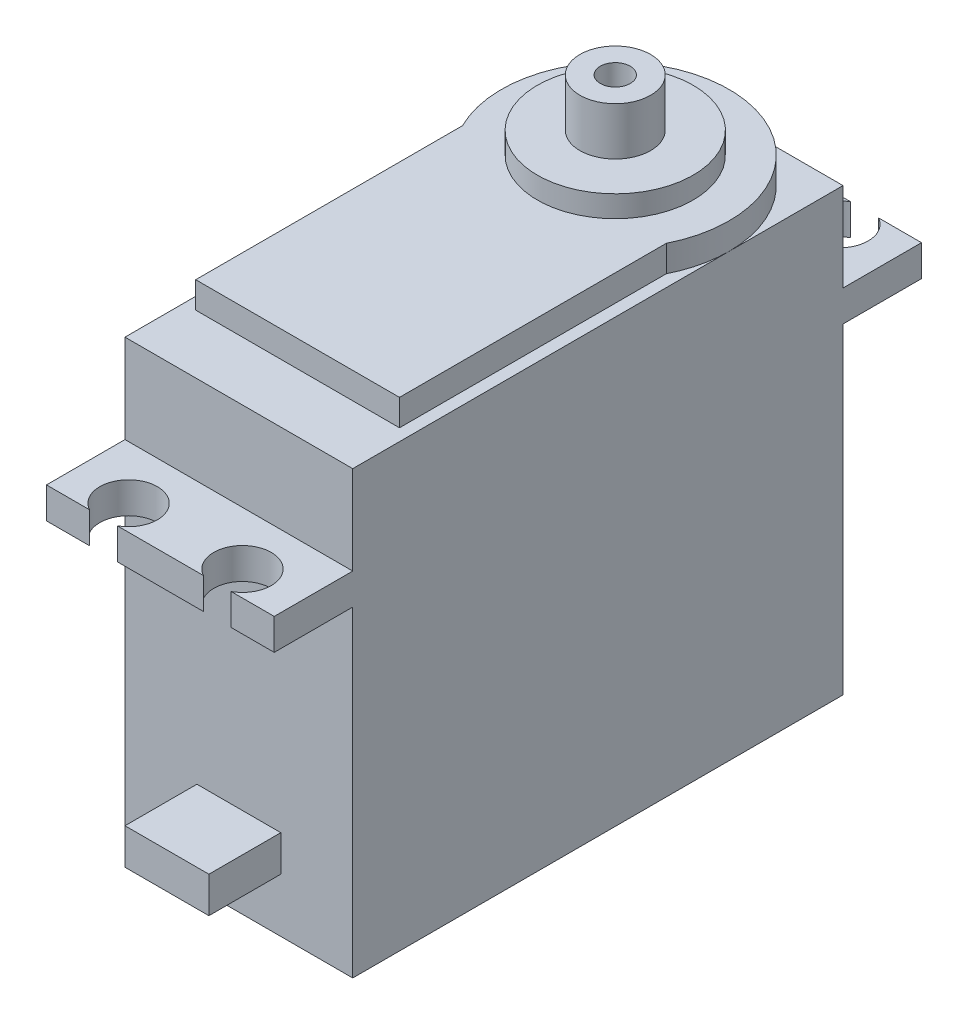
SolidWorks part; units mm, degrees
ref_plane "Front Plane" through (0, 0, 0) normal (0, 0, 1) x (1, 0, 0)
ref_plane "Top Plane" through (0, 0, 0) normal (0, 1, 0) x (1, 0, 0)
ref_plane "Right Plane" through (0, 0, 0) normal (1, 0, 0) x (0, 0, -1)
sketch "Sketch1" plane through (0, 0, 0) normal (1, 0, 0) x (0, 0, -1)
  line L1 (-20.45, 18.4) -> (20.45, 18.4)
  line L2 (-20.45, 18.4) -> (-20.45, -18.4)
  line L3 (-20.45, -18.4) -> (20.45, -18.4)
  line L4 (20.45, 18.4) -> (20.45, -18.4)
  line L5 (-20.45, 18.4) -> (20.45, -18.4) construction
  line L6 (-20.45, -18.4) -> (20.45, 18.4) construction
  point P0 (0, 0)
  dimension "D1" = 36.8
  dimension "D2" = 40.9
extrude "Boss-Extrude1" add sketch "Sketch1" along normal blind 19
sketch "Sketch2" plane through (0, 0, 20.45) normal (0, 0, 1) x (1, 0, 0)
  line L0 (19, 18.4) -> (19, -18.4) construction
  line L1 (0, 8.4) -> (19, 8.4)
  line L2 (0, 8.4) -> (0, -18.4)
  line L3 (0, -18.4) -> (19, -18.4)
  line L4 (19, 8.4) -> (19, -18.4)
  line L5 (0, 8.4) -> (19, -18.4) construction
  line L6 (0, -18.4) -> (19, 8.4) construction
  line L7 (19, -18.4) -> (0, -18.4) construction
  line L8 (0, 18.4) -> (0, -18.4) construction
  line L10 (0, 11) -> (19, 11)
  line L11 (0, 11) -> (0, 8.4)
  line L12 (0, 8.4) -> (19, 8.4)
  line L13 (19, 11) -> (19, 8.4)
  line L14 (0, 11) -> (19, 8.4) construction
  line L15 (0, 8.4) -> (19, 11) construction
  point P0 (9.5, -5)
  point P11 (9.5, 9.7)
  line M4 (0, 18.4) -> (0, -18.4)
  line M6 (19, -18.4) -> (19, 18.4)
  dimension "D1" = 26.8
  dimension "D2" = 2.6
extrude "Boss-Extrude2" add sketch "Sketch2" along normal blind 6.55 from surface contours L10 L1 M4 M6 region at (9.5, 9.7, 20.45) starting at face at (9.5, 0, 20.45)
sketch "Sketch3" plane through (0, 0, -20.45) normal (0, 0, -1) x (-1, 0, 0)
  line L0 (0, -18.4) -> (0, 18.4) construction
  line L1 (-19, 8.4) -> (0, 8.4)
  line L2 (-19, 8.4) -> (-19, -18.4)
  line L3 (-19, -18.4) -> (0, -18.4)
  line L4 (0, 8.4) -> (0, -18.4)
  line L5 (-19, 8.4) -> (0, -18.4) construction
  line L6 (-19, -18.4) -> (0, 8.4) construction
  line L7 (-19, -18.4) -> (0, -18.4) construction
  line L8 (-19, -18.4) -> (-19, 18.4) construction
  line L14 (-19, 11) -> (0, 11)
  line L15 (-19, 11) -> (-19, 8.4)
  line L16 (-19, 8.4) -> (0, 8.4)
  line L17 (0, 11) -> (0, 8.4)
  line L18 (-19, 11) -> (0, 8.4) construction
  line L19 (-19, 8.4) -> (0, 11) construction
  point P0 (-9.5, -5)
  point P11 (-9.5, 9.7)
  line M4 (0, -18.4) -> (0, 18.4)
  line M6 (-19, 18.4) -> (-19, -18.4)
  dimension "D1" = 26.8
  dimension "D2" = 2.6
extrude "Boss-Extrude3" add sketch "Sketch3" along normal blind 6.55 from surface contours L14 L1 M6 M4 region at (9.5, 9.7, -20.45) starting at face at (9.5, 0, -20.45)
sketch "Sketch4" plane through (0, 18.4, 0) normal (0, 1, 0) x (1, 0, 0)
  line L0 (19, 20.45) -> (0, 20.45) construction
  line L1 (19, 20.45) -> (19, -20.45) construction
  line L2 (0, 20.45) -> (0, -20.45) construction
  line L3 (9.5, 20.45) -> (9.5, -20.45) construction
  line L4 (1, 10.95) -> (18, 10.95)
  line L5 (1, 10.95) -> (1, -15.55)
  line L6 (1, -15.55) -> (18, -15.55)
  line L7 (18, 10.95) -> (18, -15.55)
  line L8 (1, 10.95) -> (18, -15.55) construction
  line L9 (1, -15.55) -> (18, 10.95) construction
  line L10 (0, -20.45) -> (19, -20.45) construction
  circle A0 centre (9.5, 10.95) radius 9.5
  circle A1 centre (9.5, 10.95) radius 6.5
  circle A2 centre (9.5, 10.95) radius 2.95
  circle A3 centre (9.5, 10.95) radius 1.25
  point P8 (9.5, -2.3)
  dimension "D1" = 26.5
  dimension "D3" = 13
  dimension "D4" = 5.9
  dimension "D5" = 2.5
  dimension "D2" = 17
extrude "Boss-Extrude4" add sketch "Sketch4" along normal blind 2.2 from surface contours A1 L4 L7 A0 L5 | A1 L4 L5 A0 L7 | A2 L4 A1 | A3 L4 A2 | A3 L4 A2 | L4 A3 | L4 A3 | A2 L4 A1 | A0 L5 L6 L7 region at (9.5, 18.4, -12.3599) region at (9.5, 18.4, -10.4195) region at (9.5, 18.4, -11.4805) region at (9.5, 18.4, -9.5401) region at (9.5, 18.4, -14.0995) region at (9.5, 18.4, -7.8005) region at (9.5, 18.4, -17.6845) region at (17, 18.4, -10.7553) region at (9.5, 18.4, 6.2439) starting at face at (9.5, 18.4, 0)
extrude "Boss-Extrude5" add sketch "Sketch4<4>" along normal blind 1.8 from surface contours A2 L4 A1 | A3 L4 A2 | A3 L4 A2 | A2 L4 A1 | L4 A3 | L4 A3 region at (9.5, 18.4, -12.3599) region at (9.5, 18.4, -10.4195) region at (9.5, 18.4, -11.4805) region at (9.5, 18.4, -9.5401) region at (9.5, 18.4, -14.0995) region at (9.5, 18.4, -7.8005) starting at face at (9.5, 20.6, 0.9857)
sketch "Sketch4<4>" plane through (0, 18.4, 0) normal (0, 1, 0) x (1, 0, 0) same geometry as "Sketch4"
extrude "Boss-Extrude6" add sketch "Sketch4<6>" along normal blind 4 from surface contours A3 L4 A2 | A3 L4 A2 region at (9.5, 18.4, -12.3599) region at (9.5, 18.4, -9.5401) starting at face at (9.5, 22.4, -17.45)
sketch "Sketch4<6>" plane through (0, 18.4, 0) normal (0, 1, 0) x (1, 0, 0) same geometry as "Sketch4"
sketch "Sketch8" plane through (0, 11, 0) normal (0, 1, 0) x (1, 0, 0)
  line L0 (9.5, -24.75) -> (0, -24.75) construction
  line L1 (0, -22.5) -> (19, -22.5)
  line L2 (0, -22.5) -> (0, -27)
  line L3 (0, -27) -> (19, -27)
  line L4 (19, -22.5) -> (19, -27)
  line L5 (0, -22.5) -> (19, -27) construction
  line L6 (0, -27) -> (19, -22.5) construction
  line L7 (19, -27) -> (19, -20.45) construction
  line L8 (0, -27) -> (19, -27) construction
  line L9 (0, -27) -> (0, -20.45) construction
  line L10 (9.5, -27) -> (9.5, 27) construction
  line L11 (19, 27) -> (0, 27) construction
  line L12 (9.5, -24.75) -> (19, -24.75) construction
  line L13 (4.75, -24.75) -> (4.75, -22.5) construction
  line L14 (4.75, -22.5) -> (4.75, -27) construction
  line L15 (14.25, -24.75) -> (14.25, -22.5) construction
  line L16 (14.25, -22.5) -> (14.25, -27) construction
  circle A0 centre (4.75, -24.9) radius 2.4
  circle A1 centre (14.25, -24.9) radius 2.4
  point P0 (9.5, -24.75)
  dimension "D1" = 4.8
  dimension "D2" = 4.8
  dimension "D3" = 4.5
extrude "Cut-Extrude1" cut sketch "Sketch8" against normal blind 2.6 from surface contours L3 A0 | L3 A1 region at (4.75, 11, 24.8407) region at (14.25, 11, 24.8407) starting at face at (9.5, 11, 23.725)
mirror "Mirror1" about plane through (0, 0, 0) normal (0, 0, 1) of "Cut-Extrude1"
sketch "Sketch9" plane through (0, 0, 20.45) normal (0, 0, 1) x (1, 0, 0)
  line L0 (19, 8.4) -> (19, -18.4) construction
  line L1 (0, -12.4) -> (19, -12.4)
  line L2 (0, -12.4) -> (0, -18.4)
  line L3 (0, -18.4) -> (19, -18.4)
  line L4 (19, -12.4) -> (19, -18.4)
  line L5 (0, -12.4) -> (19, -18.4) construction
  line L6 (0, -18.4) -> (19, -12.4) construction
  line L7 (19, -18.4) -> (0, -18.4) construction
  line L8 (0, 8.4) -> (0, -18.4) construction
  line L12 (6, -10.9) -> (13, -10.9)
  line L13 (6, -10.9) -> (6, -13.9)
  line L14 (6, -13.9) -> (13, -13.9)
  line L15 (13, -10.9) -> (13, -13.9)
  line L16 (6, -10.9) -> (13, -13.9) construction
  line L17 (6, -13.9) -> (13, -10.9) construction
  point P0 (9.5, -15.4)
  point P15 (9.5, -12.4)
  point P20 (9.5, -12.4)
  dimension "D1" = 6
  dimension "D2" = 3
  dimension "D3" = 7
extrude "Boss-Extrude7" add sketch "Sketch9" along normal blind 6 from surface contours L15 L12 L13 L1 | L15 L1 L13 L14 region at (9.5, -11.65, 20.45) region at (9.5, -13.15, 20.45) starting at face at (9.5, -5, 20.45)
